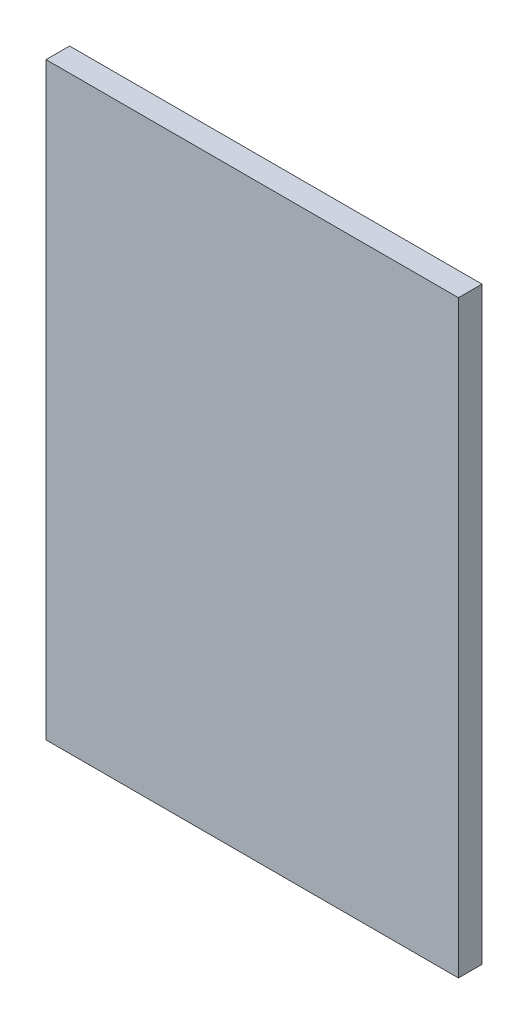
SolidWorks part; units mm, degrees
ref_plane "Front Plane" through (0, 0, 0) normal (1, 0, 0) x (0, 1, 0)
ref_plane "Top Plane" through (0, 0, 0) normal (0, 0, 1) x (0, 1, 0)
ref_plane "Right Plane" through (0, 0, 0) normal (0, 1, 0) x (-1, 0, 0)
sketch "Sketch1" plane through (0, 0, 0) normal (0, 0, 1) x (0, 1, 0)
  line L1 (-125, -87.5) -> (125, -87.5)
  line L2 (-125, -87.5) -> (-125, 87.5)
  line L3 (-125, 87.5) -> (125, 87.5)
  line L4 (125, -87.5) -> (125, 87.5)
  line L5 (-125, -87.5) -> (125, 87.5) construction
  line L6 (-125, 87.5) -> (125, -87.5) construction
  point P0 (0, 0)
  dimension "D1" = 250
  dimension "D2" = 175
extrude "Boss-Extrude1" add sketch "Sketch1" along normal blind 10
